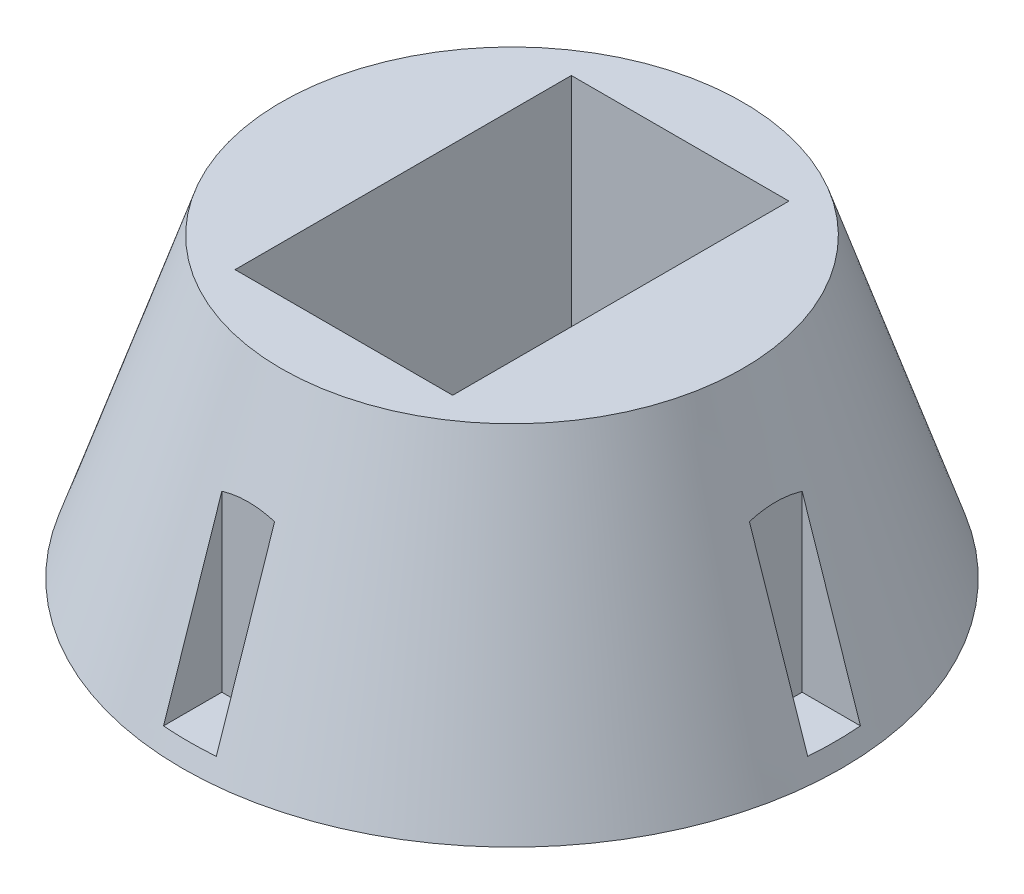
SolidWorks part; units mm, degrees
ref_plane "Plan de face" through (0, 0, 0) normal (0, 0, 1) x (1, 0, 0)
ref_plane "Plan de dessus" through (0, 0, 0) normal (0, 1, 0) x (1, 0, 0)
ref_plane "Plan de droite" through (0, 0, 0) normal (1, 0, 0) x (0, 0, -1)
sketch "Esquisse1" plane through (0, 0, 0) normal (0, 0, 1) x (1, 0, 0)
  line L0 (0, 185.6249) -> (0, -69.8928) construction
  line L1 (0, 0) -> (-50, 0)
  line L2 (-50, 0) -> (-35, 45)
  line L3 (-35, 45) -> (0, 45)
  line L4 (0, 45) -> (0, 0)
  dimension "D1" = 70
  dimension "D2" = 100
  dimension "D3" = 45
revolve "Révolution1" add sketch "Esquisse1" angle 360 about L0
sketch "Esquisse2" plane through (0, 45, 0) normal (0, 1, 0) x (1, 0, 0)
  line L0 (0, 36.703) -> (0, -41.6533) construction
  line L2 (16.5, -25.5) -> (-16.5, -25.5)
  line L3 (16.5, -25.5) -> (16.5, 25.5)
  line L4 (16.5, 25.5) -> (-16.5, 25.5)
  line L5 (-16.5, -25.5) -> (-16.5, 25.5)
  line L6 (16.5, -25.5) -> (-16.5, 25.5) construction
  line L7 (16.5, 25.5) -> (-16.5, -25.5) construction
  point P3 (0, 0)
  dimension "D1" = 33
  dimension "D2" = 51
extrude "Enlèv. mat.-Extru.1" cut sketch "Esquisse2" against normal blind 41
sketch "Esquisse3" plane through (0, 45, 0) normal (0, 1, 0) x (1, 0, 0)
  line L0 (0, -70.9025) -> (0, 59.7007) construction
  line L1 (-119.6559, 0) -> (92.9243, 0) construction
  line L7 (4, -52) -> (-4, -40) construction
  line L8 (4, 40) -> (-4, 40)
  line L18 (4, 40) -> (4, 52)
  line L19 (4, 52) -> (-4, 52)
  line L24 (-4, 40) -> (-4, 52)
  line L25 (4, 40) -> (-4, 52) construction
  line L26 (4, 52) -> (-4, 40) construction
  line L27 (52, -4) -> (40, -4)
  line L28 (52, -4) -> (52, 4)
  line L29 (52, 4) -> (40, 4)
  line L30 (40, -4) -> (40, 4)
  line L31 (52, -4) -> (40, 4) construction
  line L32 (52, 4) -> (40, -4) construction
  line L33 (4, -40) -> (-4, -52) construction
  line L34 (-4, -40) -> (-4, -52)
  line L35 (4, -52) -> (-4, -52)
  line L36 (4, -40) -> (4, -52)
  line L37 (4, -40) -> (-4, -40)
  line L38 (-52, 4) -> (-40, -4) construction
  line L39 (-52, -4) -> (-40, 4) construction
  line L40 (-40, -4) -> (-40, 4)
  line L41 (-52, 4) -> (-40, 4)
  line L42 (-52, -4) -> (-52, 4)
  line L43 (-52, -4) -> (-40, -4)
  point P4 (0, 46)
  point P5 (0, 0)
  point P10 (46, 0)
  point P19 (0, -46)
  point P24 (-46, 0)
  dimension "D1" = 12
  dimension "D2" = 8
  dimension "D4" = 40
  dimension "D3" = 40
  dimension "D5" = 8
  dimension "D6" = 12
extrude "Enlèv. mat.-Extru.3" cut sketch "Esquisse3" against normal blind 42
